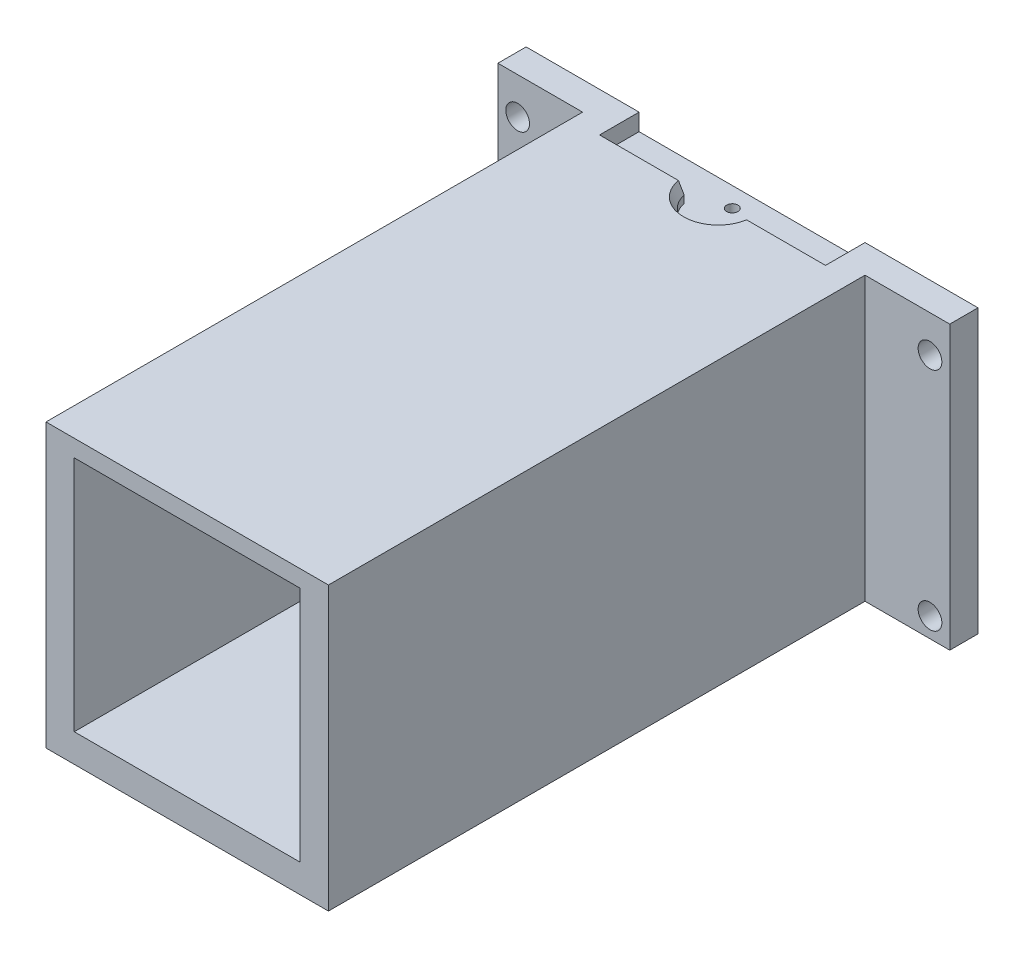
SolidWorks part; units mm, degrees
ref_plane "前基準面" through (0, 0, 0) normal (0, 0, 1) x (1, 0, 0)
ref_plane "上基準面" through (0, 0, 0) normal (0, 1, 0) x (1, 0, 0)
ref_plane "右基準面" through (0, 0, 0) normal (1, 0, 0) x (0, 0, -1)
sketch "草圖1" plane through (0, 0, 0) normal (0, 0, 1) x (1, 0, 0)
  line L1 (0, 0) -> (80, 0)
  line L2 (0, 0) -> (0, 50)
  line L3 (0, 50) -> (80, 50)
  line L4 (80, 0) -> (80, 50)
extrude "填料-伸長1" add sketch "草圖1" along normal blind 5
sketch "草圖2" plane through (0, 0, 0) normal (0, 0, 1) x (1, 0, 0)
  line L0 (80, 50) -> (0, 50) construction
  line L1 (15, 0) -> (65, 0)
  line L2 (15, 0) -> (15, 50)
  line L3 (15, 50) -> (65, 50)
  line L4 (65, 0) -> (65, 50)
extrude "填料-伸長2" add sketch "草圖2" along normal blind 100
sketch "草圖4" plane through (0, 0, 0) normal (0, 0, 1) x (1, 0, 0)
  line L1 (20, 5) -> (60, 5)
  line L2 (20, 5) -> (20, 47)
  line L3 (20, 47) -> (60, 47)
  line L4 (60, 5) -> (60, 47)
extrude "除料-伸長1" cut sketch "草圖4" along normal through all
sketch "草圖5" plane through (0, 0, 0) normal (0, 0, 1) x (1, 0, 0)
  circle A0 centre (76.5, 3.5) radius 2.1
  circle A1 centre (76.5, 43.5) radius 2.1
  circle A2 centre (3.5, 3.5) radius 2.1
  circle A3 centre (3.5, 43.5) radius 2.1
extrude "除料-伸長2" cut sketch "草圖5" along normal blind 10
sketch "草圖7" plane through (0, 0, 0) normal (0, 1, 0) x (1, 0, 0)
  line L0 (0, 0) -> (80, 0) construction
  line L1 (60, 0) -> (20, 0)
  line L2 (60, 0) -> (60, -7)
  line L3 (60, -7) -> (20, -7)
  line L4 (20, 0) -> (20, -7)
  point P6 (0, 0)
  point P7 (0, 0)
sketch "草圖8" plane through (0, 0, 0) normal (0, 1, 0) x (1, 0, 0)
  line L0 (0, 0) -> (80, 0) construction
  line L1 (15, 0) -> (65, 0)
  line L2 (15, 0) -> (15, -15)
  line L3 (15, -15) -> (65, -15)
  line L4 (65, 0) -> (65, -15)
  point P6 (0, 0)
  point P7 (0, 0)
  point P8 (0, 0)
  point P9 (0, 0)
  point P10 (0, 0)
extrude "除料-伸長7" cut sketch "草圖7" along normal through all from offset 10
extrude "填料-伸長6" add sketch "草圖8" along normal blind 2.5 from offset 44.5
sketch "草圖9" plane through (0, 0, 0) normal (0, 1, 0) x (1, 0, 0)
  circle A0 centre (40, -3.5) radius 1
  point P2 (0, 0)
extrude "除料-伸長8" cut sketch "草圖9" along normal through all from offset 10
chamfer "導角2" distance 4.4 angle 30 1 edges at (40, 44.5, 15) first distance on face at (40, 44.5, 4.5)
sketch "草圖14" plane through (0, 0, 0) normal (0, 1, 0) x (1, 0, 0)
  circle A0 centre (40, -6) radius 5.1114
extrude "除料-伸長9" cut sketch "草圖14" along normal through all from offset 47
chamfer "導角3" distance 1 angle 60 1 edges at (40, 50, 11.1114) first distance on face at (40, 50, 18.008)
